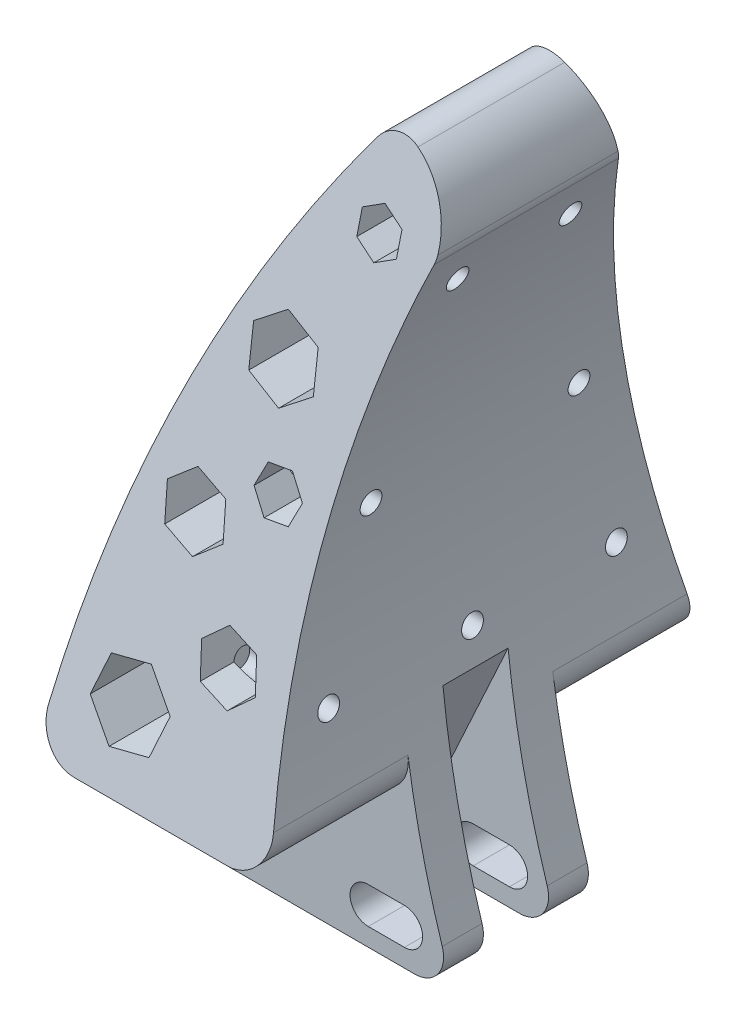
SolidWorks part; units mm, degrees
material "Polylactide (PLA)"
ref_plane "Front Plane" through (0, 0, 0) normal (0, 0, 1) x (1, 0, 0)
ref_plane "Top Plane" through (0, 0, 0) normal (0, 1, 0) x (1, 0, 0)
ref_plane "Right Plane" through (0, 0, 0) normal (1, 0, 0) x (0, 0, -1)
sketch "Sketch5" plane through (0, 0, 0) normal (0, 0, 1) x (1, 0, 0)
  line L0 (-5.5914, 0) -> (-33.738, 0)
  line L8 (-23.7932, 26.0296) -> (-22.1489, 31.13)
  line L9 (-22.1489, 31.13) -> (-25.7438, 35.1043)
  line L10 (-25.7438, 35.1043) -> (-30.9831, 33.9782)
  line L11 (-30.9831, 33.9782) -> (-32.6275, 28.8777)
  line L12 (-32.6275, 28.8777) -> (-29.0326, 24.9034)
  line L13 (-29.0326, 24.9034) -> (-23.7932, 26.0296)
  line L14 (-19.7045, 50.5377) -> (-20.4487, 55.0061)
  line L15 (-20.4487, 55.0061) -> (-24.6905, 56.5958)
  line L16 (-24.6905, 56.5958) -> (-28.1882, 53.7172)
  line L17 (-28.1882, 53.7172) -> (-27.444, 49.2488)
  line L18 (-27.444, 49.2488) -> (-23.2022, 47.6591)
  line L19 (-23.2022, 47.6591) -> (-19.7045, 50.5377)
  line L20 (-12.0209, 69.6144) -> (-12.6014, 74.6171)
  line L21 (-12.6014, 74.6171) -> (-17.2242, 76.6158)
  line L22 (-17.2242, 76.6158) -> (-21.2664, 73.6117)
  line L23 (-21.2664, 73.6117) -> (-20.6859, 68.6089)
  line L24 (-20.6859, 68.6089) -> (-16.0632, 66.6103)
  line L25 (-16.0632, 66.6103) -> (-12.0209, 69.6144)
  line L26 (-4.9947, 87.3663) -> (-5.0097, 90.5214)
  line L27 (-5.0097, 90.5214) -> (-7.7495, 92.0859)
  line L28 (-7.7495, 92.0859) -> (-10.4745, 90.4954)
  line L29 (-10.4745, 90.4954) -> (-10.4595, 87.3403)
  line L30 (-10.4595, 87.3403) -> (-7.7196, 85.7757)
  line L31 (-7.7196, 85.7757) -> (-4.9947, 87.3663)
  line L32 (-12.0209, 37.6377) -> (-12.8753, 41.812)
  line L33 (-12.8753, 41.812) -> (-16.9175, 43.1593)
  line L34 (-16.9175, 43.1593) -> (-20.1054, 40.3322)
  line L35 (-20.1054, 40.3322) -> (-19.251, 36.1579)
  line L36 (-19.251, 36.1579) -> (-15.2088, 34.8106)
  line L37 (-15.2088, 34.8106) -> (-12.0209, 37.6377)
  line L44 (-12.0209, 55.801) -> (-10.8206, 58.8278)
  line L45 (-10.8206, 58.8278) -> (-12.8417, 61.3807)
  line L46 (-12.8417, 61.3807) -> (-16.0632, 60.9068)
  line L47 (-16.0632, 60.9068) -> (-17.2635, 57.88)
  line L48 (-17.2635, 57.88) -> (-15.2423, 55.3271)
  line L49 (-15.2423, 55.3271) -> (-12.0209, 55.801)
  arc A0 (-38.7378, 4.9662) -> (-10.2446, 98.071) centre (124.0248, 6.0676) cw
  arc A1 (-4.9947, 99.3023) -> (0.0615, 90.0404) centre (-9.8234, 90.6553) cw
  arc A2 (-0.1684, 88.9308) -> (-1.7795, 5.2121) centre (122.394, 44.6973) ccw
  arc A3 (-33.738, 0) -> (-38.7378, 4.9662) centre (-33.738, 5) cw
  arc A4 (-1.7795, 5.2121) -> (-5.5914, 0) centre (-5.5914, 4) cw
  arc A5 (-10.2446, 98.071) -> (-4.9947, 99.3023) centre (-6.9449, 95.81) cw
  arc A6 (0.0615, 90.0404) -> (-0.1684, 88.9308) centre (-3.9308, 90.2887) cw
  circle A8 centre (-27.3882, 30.0039) radius 4.641 construction
  circle A9 centre (-23.9464, 52.1275) radius 3.923 construction
  circle A10 centre (-16.6437, 71.613) radius 4.3616 construction
  circle A11 centre (-7.7346, 88.9308) radius 2.7324 construction
  circle A12 centre (-16.0632, 38.985) radius 3.69 construction
  circle A14 centre (-14.042, 58.3539) radius 2.8199 construction
  point P12 (0, 0)
  dimension "D1" = 5
  dimension "D2" = 4
  dimension "D3" = 4
  dimension "D4" = 4
  dimension "D5" = 98.071
extrude "Boss-Extrude4" add sketch "Sketch5" along normal blind 60
sketch "Sketch7" plane through (0, 0, 60) normal (0, 0, 1) x (1, 0, 0)
  line L1 (-12, 5) -> (-7, 5) construction
  line L2 (-12, 7.5121) -> (-7, 7.5121)
  line L3 (-12, 2.4879) -> (-7, 2.4879)
  arc A2 (-12, 7.5121) -> (-12, 2.4879) centre (-12, 5) ccw
  arc A3 (-7, 2.4879) -> (-7, 7.5121) centre (-7, 5) ccw
  point P6 (-9.5, 5)
  dimension "D1" = 2.5121
  dimension "D2" = 5
  dimension "D3" = 7
extrude "Cut-Extrude2" cut sketch "Sketch7" against normal blind 60
sketch "Sketch8" plane through (0, 0, 60) normal (0, 0, 1) x (1, 0, 0)
  circle A0 centre (-32.2838, 6.1708) radius 2.5
  dimension "D1" = 5
extrude "Cut-Extrude3" cut sketch "Sketch8" against normal blind 60
sketch "Sketch9" plane through (0, 0, 0) normal (0, 0, 1) x (1, 0, 0)
  line L0 (0, 0) -> (-18.287, 0)
  line L1 (-33.738, 0) -> (-5.5914, 0) construction
  line L2 (-20.1042, 2.8352) -> (-7.1796, 30.9559)
  line L3 (-7.1796, 30.9559) -> (0, 0)
  arc A0 (-0.1684, 88.9308) -> (-1.7795, 5.2121) centre (122.394, 44.6973) ccw construction
  arc A1 (-18.287, 0) -> (-20.1042, 2.8352) centre (-18.287, 2) cw
  point P11 (-21.4074, 0)
  dimension "D3" = 2
  dimension "D1" = 21.4074
  dimension "D2" = 65.316
extrude "Cut-Extrude4" cut sketch "Sketch9" along normal blind 9 from offset 25.5
sketch "Sketch10" plane through (0, 0, 0) normal (0, 0, -1) x (-1, 0, 0)
  line L6 (40.8314, 20) -> (-3.0502, 20)
  line L7 (40.8314, 20) -> (40.8314, -2.7206)
  line L8 (40.8314, -2.7206) -> (-3.0502, -2.7206)
  line L9 (-3.0502, 20) -> (-3.0502, -2.7206)
extrude "Cut-Extrude5" cut sketch "Sketch10" against normal blind 20
sketch "Sketch11" plane through (0, 0, 60) normal (0, 0, 1) x (1, 0, 0)
  line L6 (-40.5856, 20) -> (3.8716, 20)
  line L7 (-40.5856, 20) -> (-40.5856, -2.7658)
  line L8 (-40.5856, -2.7658) -> (3.8716, -2.7658)
  line L9 (3.8716, 20) -> (3.8716, -2.7658)
extrude "Cut-Extrude6" cut sketch "Sketch11" against normal blind 20
fillet "Fillet1" radius 5 1 edges at (-5.5442, 20, 50)
fillet "Fillet2" radius 5 1 edges at (-5.5442, 20, 10)
fillet "Fillet3" radius 5 1 edges at (-38.1442, 20, 50)
fillet "Fillet4" radius 5 1 edges at (-38.1442, 20, 10)
sketch "Sketch12" plane through (0, 0, 0) normal (1, 0, 0) x (0, 0, -1)
  line L0 (-60, 20) -> (-60, 99.81)
  line L5 (-60, 99.81) -> (-40, 99.81)
  line L6 (-60, 20) -> (-40, 99.81)
extrude "Cut-Extrude7" cut sketch "Sketch12" against normal blind 49
extrude "Cut-Extrude8" cut sketch "Sketch12<2>" along normal blind 15
sketch "Sketch12<2>" plane through (0, 0, 0) normal (1, 0, 0) x (0, 0, -1) same geometry as "Sketch12"
sketch "Sketch13" plane through (0, 0, 0) normal (1, 0, 0) x (0, 0, -1)
  line L5 (0, 20) -> (0, 99.81)
  line L6 (0, 99.81) -> (-20, 99.81)
  line L7 (0, 20) -> (-20, 99.81)
extrude "Cut-Extrude9" cut sketch "Sketch13" against normal blind 45
extrude "Cut-Extrude10" cut sketch "Sketch13<2>" along normal blind 18
sketch "Sketch13<2>" plane through (0, 0, 0) normal (1, 0, 0) x (0, 0, -1) same geometry as "Sketch13"
sketch "Sketch14" plane through (0, 0, 0) normal (1, 0, 0) x (0, 0, -1)
  line L0 (-58.5646, 25.7279) -> (-40, 25.7279) construction
  line L1 (-42.7263, 88.9308) -> (-58.5646, 25.7279) construction
  circle A0 centre (-49.8731, 35.7279) radius 1.5
  dimension "D1" = 3
  dimension "D2" = 10
  dimension "D3" = 6
extrude "Cut-Extrude11" cut sketch "Sketch14" against normal blind 20
sketch "Sketch15" plane through (0, 0, 0) normal (1, 0, 0) x (0, 0, -1)
  line L0 (-58.5646, 25.7279) -> (-40, 25.7279) construction
  line L1 (-42.7263, 88.9308) -> (-58.5646, 25.7279) construction
  line L2 (-1.4354, 25.7279) -> (-17.2737, 88.9308) construction
  circle A0 centre (-30.0021, 35.7279) radius 1.5
  dimension "D1" = 10
  dimension "D2" = 3
  dimension "D3" = 25.275
  dimension "D4" = 25.2791
extrude "Cut-Extrude12" cut sketch "Sketch15" against normal blind 20
sketch "Sketch16" plane through (0, 0, 0) normal (1, 0, 0) x (0, 0, -1)
  line L1 (-1.4354, 25.7279) -> (-17.2737, 88.9308) construction
  line L2 (-20, 25.7279) -> (-1.4354, 25.7279) construction
  circle A0 centre (-10.1269, 35.7279) radius 1.5
  dimension "D1" = 10
  dimension "D2" = 6
  dimension "D3" = 3
extrude "Cut-Extrude13" cut sketch "Sketch16" against normal blind 20
sketch "Sketch17" plane through (0, 0, 0) normal (1, 0, 0) x (0, 0, -1)
  line L0 (-58.5646, 25.7279) -> (-40, 25.7279) construction
  line L1 (-42.7263, 88.9308) -> (-58.5646, 25.7279) construction
  circle A0 centre (-44.36, 57.7279) radius 1.5
  dimension "D1" = 32
  dimension "D2" = 6
  dimension "D3" = 3
extrude "Cut-Extrude14" cut sketch "Sketch17" against normal blind 20
sketch "Sketch18" plane through (0, 0, 0) normal (1, 0, 0) x (0, 0, -1)
  line L0 (-20, 25.7279) -> (-1.4354, 25.7279) construction
  line L1 (-1.4354, 25.7279) -> (-17.2737, 88.9308) construction
  circle A0 centre (-15.64, 57.7279) radius 1.5
  dimension "D1" = 32
  dimension "D2" = 6
  dimension "D3" = 3
extrude "Cut-Extrude15" cut sketch "Sketch18" against normal blind 20
sketch "Sketch19" plane through (0, 0, 0) normal (1, 0, 0) x (0, 0, -1)
  line L0 (-42.7263, 88.9308) -> (-17.2737, 88.9308) construction
  line L1 (-42.7263, 88.9308) -> (-58.5646, 25.7279) construction
  circle A0 centre (-37.7937, 83.9308) radius 1.5
  dimension "D1" = 5
  dimension "D2" = 6
  dimension "D3" = 3
extrude "Cut-Extrude16" cut sketch "Sketch19" against normal blind 15
sketch "Sketch20" plane through (0, 0, 0) normal (1, 0, 0) x (0, 0, -1)
  line L0 (-42.7263, 88.9308) -> (-17.2737, 88.9308) construction
  line L1 (-1.4354, 25.7279) -> (-17.2737, 88.9308) construction
  circle A0 centre (-22.2063, 83.9308) radius 1.5
  dimension "D1" = 5
  dimension "D2" = 3
  dimension "D3" = 6
extrude "Cut-Extrude17" cut sketch "Sketch20" against normal blind 15
